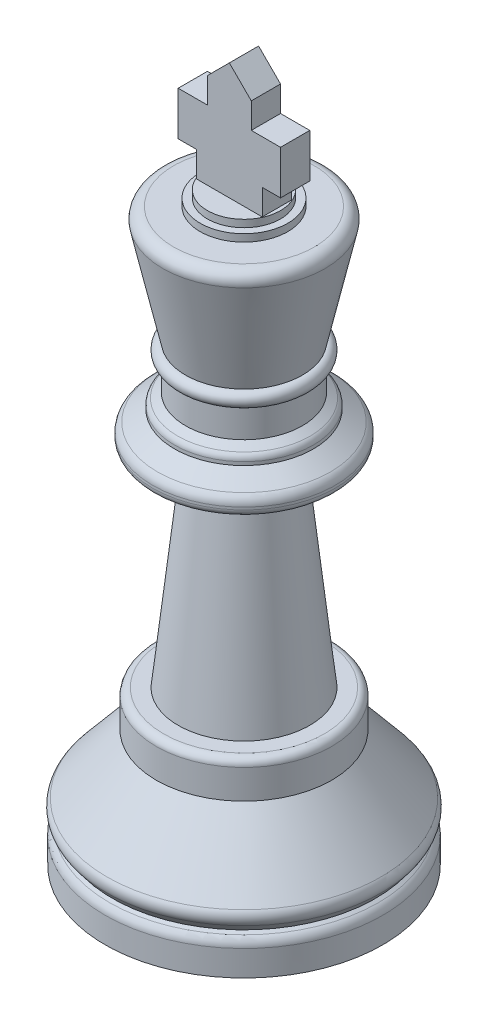
SolidWorks part; units mm, degrees
ref_plane "Front Plane" through (0, 0, 0) normal (0, 0, 1) x (1, 0, 0)
ref_plane "Top Plane" through (0, 0, 0) normal (0, 1, 0) x (1, 0, 0)
ref_plane "Right Plane" through (0, 0, 0) normal (1, 0, 0) x (0, 0, -1)
sketch "Sketch1" plane through (0, 0, 0) normal (0, 0, 1) x (1, 0, 0)
  line L0 (0, 0) -> (0, 80)
  line L1 (0, 80) -> (5, 80)
  line L2 (5, 80) -> (5, 79)
  line L3 (5, 79) -> (6, 79)
  line L4 (6, 79) -> (6, 78)
  line L5 (6, 78) -> (11.5, 78)
  line L6 (11.5, 78) -> (8, 62)
  line L8 (8, 60) -> (8, 56)
  line L9 (8, 56) -> (9.5, 55)
  line L10 (9.5, 55) -> (9.5, 54)
  line L11 (9.5, 54) -> (12.5, 52)
  line L12 (12.5, 52) -> (12.5, 50)
  line L13 (12.5, 50) -> (6, 49)
  line L14 (6, 49) -> (9, 21)
  line L15 (9, 21) -> (12, 21)
  line L16 (12, 21) -> (12, 16)
  line L17 (12, 16) -> (19.5, 7)
  line L18 (19.5, 7) -> (18, 5)
  line L19 (18, 5) -> (19, 4.25)
  line L20 (19, 4.25) -> (19, 0)
  line L21 (19, 0) -> (0, 0)
  arc A0 (8, 60) -> (8, 62) centre (8, 61) ccw
  point P3 (7.999, 62)
  point P25 (12.5714, 51.8867)
  point P26 (0, 0)
  point P27 (12.5714, 52.4244)
  point P28 (0, 0)
  point P29 (0, 0)
  point P30 (0, 0)
  point P31 (0, 0)
  point P32 (0, 0)
  point P33 (0, 0)
  point P34 (0, 0)
  point P35 (12.5714, 55)
  point P36 (11.645, 55)
  point P37 (8, 60)
  point P38 (0, 0)
  point P39 (0, 0)
  point P40 (21.2259, 7)
  point P41 (18.979, 4.5105)
  point P42 (0, 0)
  point P43 (19.4897, 7)
  dimension "D8" = 1
  dimension "D1" = 80
  dimension "D2" = 5
  dimension "D3" = 1
  dimension "D4" = 1
  dimension "D6" = 11.5
  dimension "D7" = 62
  dimension "D9" = 8
  dimension "D11" = 56
  dimension "D12" = 55
  dimension "D13" = 9.5
  dimension "D10" = 8
  dimension "D14" = 12.5
  dimension "D15" = 1
  dimension "D16" = 50
  dimension "D17" = 49
  dimension "D18" = 6
  dimension "D19" = 21
  dimension "D20" = 9
  dimension "D21" = 12
  dimension "D22" = 5
  dimension "D23" = 5
  dimension "18" = 18
  dimension "D25" = 19
  dimension "D26" = 7
  dimension "D24" = 19.5
revolve "Revolve1" add sketch "Sketch1" angle 360 about L0
sketch "Sketch2" plane through (0, 0, 0) normal (0, 0, 1) x (1, 0, 0)
  line L0 (0, 80) -> (0, 96)
  line L1 (5, 80) -> (-5, 80) construction
  line L2 (0, 96) -> (3, 93)
  line L3 (3, 93) -> (3, 89.5)
  line L4 (3, 89.5) -> (7, 89.5)
  line L5 (7, 89.5) -> (7, 83.5)
  line L6 (7, 83.5) -> (4.5, 83.5)
  line L7 (4.5, 83.5) -> (4.5, 80)
  line L8 (4.5, 80) -> (0, 80)
  point P5 (3, 87.6668)
  point P12 (3, 90.7767)
  dimension "D1" = 3.5
  dimension "D2" = 2.5
  dimension "D3" = 4.5
  dimension "D4" = 3
  dimension "D5" = 6
  dimension "D6" = 16
  dimension "D7" = 3.5
extrude "Boss-Extrude1" add sketch "Sketch2" along normal blind 2 and the other way blind 2
mirror "Mirror1" about plane through (0, 80, -2) normal (-1, 0, 0) of "Boss-Extrude1"
fillet "Fillet1" radius 1.5 4 edges at (0, 4.25, -19) (0, 7, -19.5) (0, 52, -12.5) (0, 78, -11.5)
fillet "Fillet2" radius 1 3 edges at (0, 55, -9.5) (0, 50, -12.5) (0, 21, -12)
equation "\"D6@Sketch1\"=23/2mm"
equation "\"D14@Sketch1\"=25/2"
equation "\"D13@Sketch1\"=19/2"
equation "\"D18@Sketch1\"=12/2"
equation "\"D20@Sketch1\"=18/2"
equation "\"D21@Sketch1\"=24/2"
equation "\"D25@Sketch1\"=38/2"
equation "\"D3@Sketch2\"=9/2"
